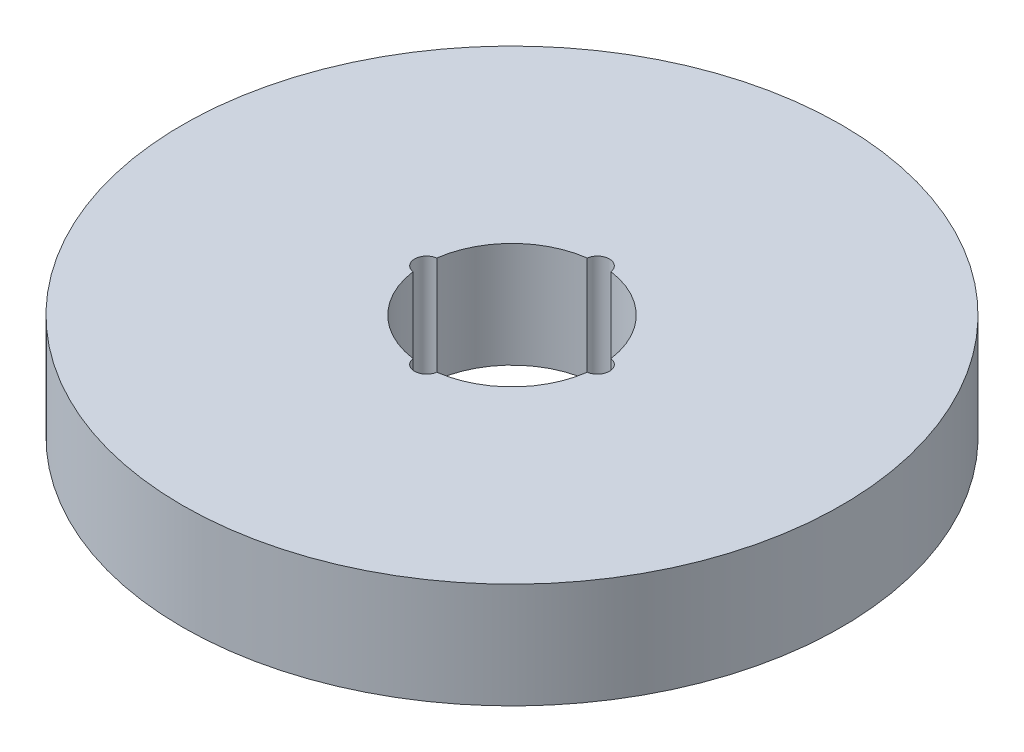
SolidWorks part; units mm, degrees
ref_plane "Front Plane" through (0, 0, 0) normal (0, 0, 1) x (1, 0, 0)
ref_plane "Top Plane" through (0, 0, 0) normal (0, 1, 0) x (1, 0, 0)
ref_plane "Right Plane" through (0, 0, 0) normal (1, 0, 0) x (0, 0, -1)
sketch "Sketch1" plane through (0, 0, 0) normal (0, 1, 0) x (1, 0, 0)
  circle A0 centre (0, 0) radius 75
  dimension "FLANGE_OD" = 150
extrude "Boss-Extrude1" add sketch "Sketch1" along normal blind 24
sketch "Sketch2" plane through (0, 0, 0) normal (0, 1, 0) x (1, 0, 0)
  circle A0 centre (0, 0) radius 20
  dimension "BORE_D" = 40
extrude "Cut-Extrude1" cut sketch "Sketch2" along normal through all
sketch "Sketch3" plane through (0, 24, 0) normal (0, 1, 0) x (1, 0, 0)
  circle A0 centre (0, 0) radius 19.4407 construction
  circle A1 centre (-19.4407, 0) radius 2.7222
  dimension "BOLT_D" = 5.4444
  dimension "BOLT_PCD" = 38.8815
extrude "Cut-Extrude2" cut sketch "Sketch3" against normal blind 23.6263
pattern_circular "CirPattern1" count 4 over 360 about axis through (0, 0, 0) along (0, 1, 0) of "Cut-Extrude2"
